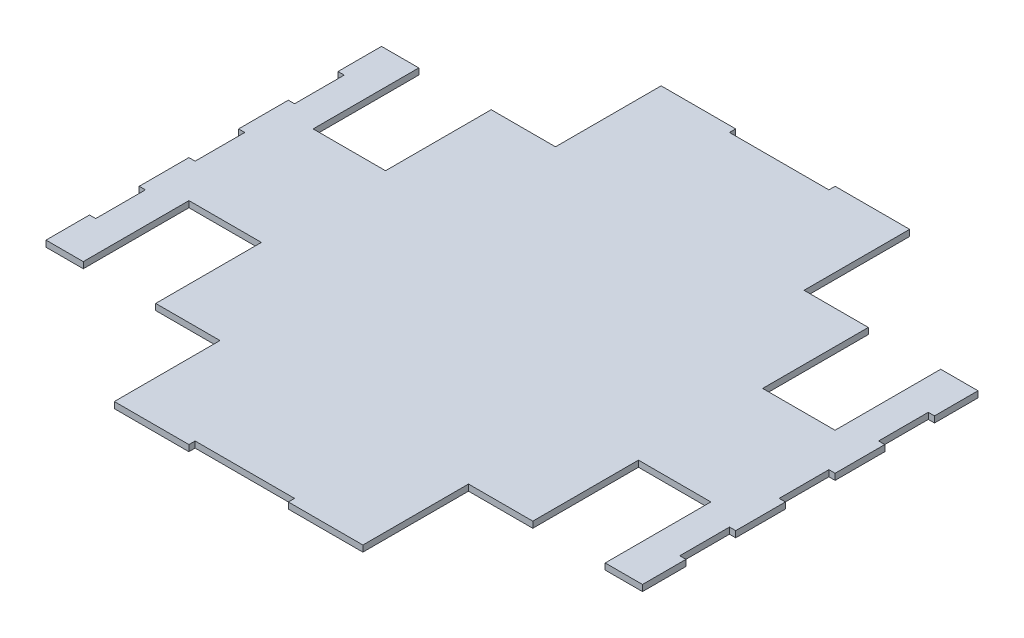
SolidWorks part; units mm, degrees
ref_plane "Front Plane" through (0, 0, 0) normal (0, 0, 1) x (1, 0, 0)
ref_plane "Top Plane" through (0, 0, 0) normal (0, 1, 0) x (1, 0, 0)
ref_plane "Right Plane" through (0, 0, 0) normal (1, 0, 0) x (0, 0, -1)
sketch "Sketch1" plane through (0, 0, 0) normal (0, 1, 0) x (1, 0, 0)
  line L0 (152.4, 85.725) -> (63.5, 85.725)
  line L1 (-152.4, -139.7) -> (152.4, -139.7)
  line L2 (-152.4, -139.7) -> (-152.4, 139.7)
  line L3 (-152.4, 139.7) -> (152.4, 139.7)
  line L4 (152.4, -139.7) -> (152.4, 139.7)
  line L5 (-152.4, -139.7) -> (152.4, 139.7) construction
  line L6 (-152.4, 139.7) -> (152.4, -139.7) construction
  line L7 (63.5, 85.725) -> (63.5, 139.7)
  line L8 (-152.4, 85.725) -> (-63.5, 85.725)
  line L9 (-63.5, 85.725) -> (-63.5, 139.7)
  line L10 (-152.4, -85.725) -> (-63.5, -85.725)
  line L11 (-63.5, -85.725) -> (-63.5, -139.7)
  line L12 (152.4, -85.725) -> (63.5, -85.725)
  line L13 (63.5, -85.725) -> (63.5, -139.7)
  line L14 (-96.35, 31.725) -> (96.35, 31.725) construction
  line L15 (96.35, 31.725) -> (133.35, 31.725)
  line L16 (96.35, 31.725) -> (96.35, 85.725)
  line L17 (96.35, 85.725) -> (133.35, 85.725)
  line L18 (133.35, 31.725) -> (133.35, 85.725)
  line L19 (96.35, 31.725) -> (133.35, 85.725) construction
  line L20 (96.35, 85.725) -> (133.35, 31.725) construction
  line L21 (96.35, -31.725) -> (133.35, -31.725)
  line L22 (96.35, -31.725) -> (96.35, -85.725)
  line L23 (96.35, -85.725) -> (133.35, -85.725)
  line L24 (133.35, -31.725) -> (133.35, -85.725)
  line L25 (96.35, -31.725) -> (133.35, -85.725) construction
  line L26 (96.35, -85.725) -> (133.35, -31.725) construction
  line L27 (-133.35, -31.725) -> (-96.35, -31.725)
  line L28 (-133.35, -31.725) -> (-133.35, -85.725)
  line L29 (-133.35, -85.725) -> (-96.35, -85.725)
  line L30 (-96.35, -31.725) -> (-96.35, -85.725)
  line L31 (-133.35, -31.725) -> (-96.35, -85.725) construction
  line L32 (-133.35, -85.725) -> (-96.35, -31.725) construction
  line L33 (-133.35, 31.725) -> (-96.35, 31.725)
  line L34 (-133.35, 31.725) -> (-133.35, 85.725)
  line L35 (-133.35, 85.725) -> (-96.35, 85.725)
  line L36 (-96.35, 31.725) -> (-96.35, 85.725)
  line L37 (-133.35, 31.725) -> (-96.35, 85.725) construction
  line L38 (-133.35, 85.725) -> (-96.35, 31.725) construction
  line L39 (-149.225, 38.1) -> (-149.225, 12.7) construction
  line L40 (152.4, 12.7) -> (149.225, 12.7)
  line L41 (152.4, 12.7) -> (152.4, -12.7)
  line L42 (152.4, -12.7) -> (149.225, -12.7)
  line L43 (149.225, 12.7) -> (149.225, -12.7)
  line L44 (152.4, 63.5) -> (149.225, 63.5)
  line L45 (152.4, 63.5) -> (152.4, 38.1)
  line L46 (152.4, 38.1) -> (149.225, 38.1)
  line L47 (149.225, 63.5) -> (149.225, 38.1)
  line L48 (152.4, -38.1) -> (149.225, -38.1)
  line L49 (152.4, -38.1) -> (152.4, -63.5)
  line L50 (152.4, -63.5) -> (149.225, -63.5)
  line L51 (149.225, -38.1) -> (149.225, -63.5)
  line L52 (-149.225, 63.5) -> (-152.4, 63.5)
  line L53 (-149.225, 63.5) -> (-149.225, 38.1)
  line L54 (-149.225, 38.1) -> (-152.4, 38.1)
  line L55 (-152.4, 63.5) -> (-152.4, 38.1)
  line L56 (-149.225, 12.7) -> (-152.4, 12.7)
  line L57 (-149.225, 12.7) -> (-149.225, -12.7)
  line L58 (-149.225, -12.7) -> (-152.4, -12.7)
  line L59 (-152.4, 12.7) -> (-152.4, -12.7)
  line L60 (-149.225, -38.1) -> (-152.4, -38.1)
  line L61 (-149.225, -38.1) -> (-149.225, -63.5)
  line L62 (-149.225, -63.5) -> (-152.4, -63.5)
  line L63 (-152.4, -38.1) -> (-152.4, -63.5)
  line L64 (-149.225, -12.7) -> (-149.225, -38.1) construction
  line L65 (149.225, 38.1) -> (149.225, 12.7) construction
  line L66 (149.225, -12.7) -> (149.225, -38.1) construction
  line L68 (25.4, -139.7) -> (-25.4, -139.7)
  line L69 (25.4, -139.7) -> (25.4, -136.525)
  line L70 (25.4, -136.525) -> (-25.4, -136.525)
  line L71 (-25.4, -139.7) -> (-25.4, -136.525)
  line L72 (25.4, 139.7) -> (-25.4, 139.7)
  line L73 (25.4, 139.7) -> (25.4, 136.525)
  line L74 (25.4, 136.525) -> (-25.4, 136.525)
  line L75 (-25.4, 139.7) -> (-25.4, 136.525)
  point P0 (0, 0)
  point P18 (114.85, 58.725)
  point P23 (114.85, -58.725)
  point P28 (-114.85, -58.725)
  point P33 (-114.85, 58.725)
  point P38 (0, 31.725)
  point P43 (149.225, 0)
  point P68 (0, -136.525)
  dimension "D1" = 304.8
  dimension "D2" = 279.4
  dimension "D3" = 53.975
  dimension "D4" = 88.9
  dimension "D5" = 54
  dimension "D6" = 37
  dimension "D7" = 19.05
  dimension "D8" = 25.4
  dimension "D9" = 3.175
  dimension "D10" = 50.8
  dimension "D11" = 3.175
extrude "Boss-Extrude1" add sketch "Sketch1" along normal blind 3.175 contours L13 L12 L4 L0 L7 L3 L9 L8 L2 L10 L11 L1 region at (0, 0, 0)
